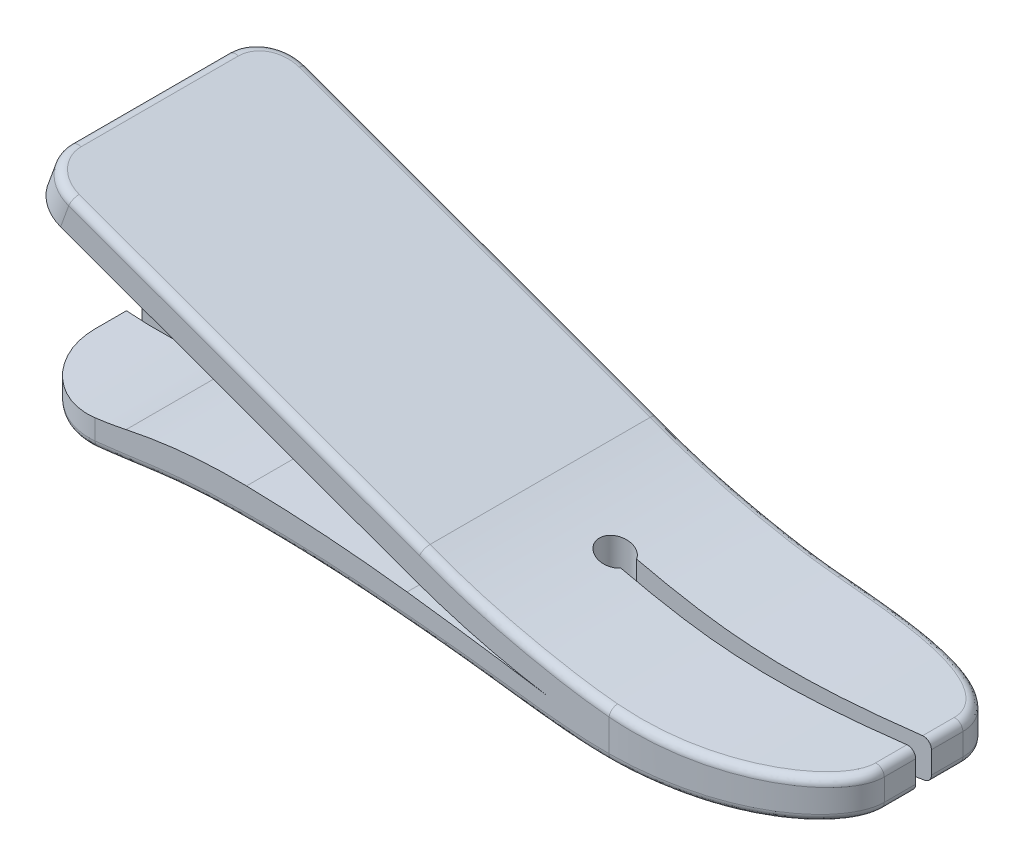
SolidWorks part; units mm, degrees
material "Thornel Mat VMA"
ref_plane "Front Plane" through (0, 0, 0) normal (0, 0, 1) x (1, 0, 0)
ref_plane "Top Plane" through (0, 0, 0) normal (0, 1, 0) x (1, 0, 0)
ref_plane "Right Plane" through (0, 0, 0) normal (1, 0, 0) x (0, 0, -1)
sketch "Sketch2" plane through (0, 0, 0) normal (0, 0, 1) x (1, 0, 0)
  line L0 (144.78, 174.4323) -> (144.78, 137.3355) construction
  line L1 (46.11, 139.37) -> (144.78, 103.46)
  line L2 (44.26, 97.84) -> (44.26, 91.84)
  line L3 (245.06, 96.26) -> (245.06, 92.26)
  line L4 (48.846, 146.8876) -> (147.516, 110.9776)
  line L5 (245.06, 101.76) -> (245.06, 96.26)
  line L6 (48.846, 146.8876) -> (46.11, 139.37)
  arc A0 (144.78, 103.46) -> (179.17, 94.55) centre (208.4691, 278.4588) ccw
  arc A3 (179.17, 94.55) -> (143.65, 99.57) centre (18.7037, -912.6868) ccw
  arc A4 (143.65, 99.57) -> (102.8, 102.5) centre (94.6418, -297.4717) ccw
  arc A5 (102.8, 102.5) -> (72.17, 99.6) centre (100.0611, -31.7796) ccw
  arc A6 (72.17, 99.6) -> (44.26, 97.84) centre (52.2393, 193.4826) cw
  spline S0 degree 3 poles (44.26, 91.84) (53.5686, 89.6988) (67.9986, 91.4707) (87.3947, 94.2323) (104.492, 94.6368) (123.2628, 94.2573) (142.8062, 92.7184) (161.4431, 90.8285) (176.9982, 88.6534) (190.5134, 87.509) (212.5929, 87.8654) (230.8283, 89.479) (245.06, 92.26) knots 0 0 0 0 0.139004 0.215092 0.291514 0.393025 0.494409 0.58308 0.671708 0.728105 0.784648 1 1 1 1
  spline S1 degree 3 poles (245.06, 101.76) (230.7908, 100.0488) (212.4954, 98.2461) (190.4741, 100.0364) (172.1057, 103.16) (157.7493, 106.9657) (147.516, 110.9776) knots 0 0 0 0 0.436365 0.551893 0.667816 1 1 1 1
  point P0 (44.26, 97.84)
  point P1 (72.17, 99.6)
  point P2 (102.8, 102.5)
  point P3 (143.65, 99.57)
  point P4 (179.17, 94.55)
  point P5 (201.9143, 92.75)
  point P6 (245.06, 96.26)
  point P7 (144.78, 103.46)
  point P10 (46.11, 139.37)
  point P27 (161.7621, 98.1831)
  point P28 (161.4321, 97.2162)
  point P29 (190.5094, 93.2003)
  point P30 (223.5612, 93.6297)
  point P31 (123.2625, 101.5581)
  point P32 (87.4017, 101.93)
  point P33 (58.2794, 97.698)
  point P34 (44.26, 91.84)
  point P35 (58.2794, 90.698)
  point P36 (72.17, 92.1)
  point P37 (87.4017, 93.93)
  point P38 (102.8, 94.5)
  point P39 (123.2625, 94.0581)
  point P40 (143.65, 92.57)
  point P41 (161.4321, 90.7162)
  point P42 (179.17, 88.55)
  point P43 (190.5094, 87.7003)
  point P44 (201.9098, 87.75)
  point P45 (223.5612, 89.1297)
  point P46 (245.06, 92.26)
  point P53 (161.7621, 106.1831)
  point P55 (179.17, 102.05)
  point P57 (245.06, 101.76)
  point P59 (223.5612, 99.6297)
  point P61 (201.92, 99.25)
  point P63 (190.5094, 100.2003)
  dimension "D1" = 70.002
  dimension "D2" = 105.0014
  dimension "D3" = 6
  dimension "D4" = 7
  dimension "D5" = 7.5
  dimension "D6" = 8
  dimension "D7" = 8
  dimension "D8" = 7.5
  dimension "D9" = 7
  dimension "D10" = 6.5
  dimension "D11" = 6
  dimension "D12" = 5.5
  dimension "D13" = 5
  dimension "D14" = 4.5
  dimension "D15" = 4
  dimension "D17" = 8
  dimension "D18" = 7.5
  dimension "D19" = 7
  dimension "D20" = 6.5
  dimension "D21" = 6
  dimension "D22" = 5.5
  dimension "D16" = 8
extrude "Boss-Extrude1" add sketch "Sketch2" along normal blind 60
fillet "Fillet1" radius 20 1 edges at (245.06, 97.01, 60) second distance 50 first distance on face at (245.06, 97.01, 30)
fillet "Fillet2" radius 50 1 edges at (245.06, 97.01, 0) second distance 20 first distance on face at (117.6568, 106.2926, 0)
fillet "Fillet3" radius 20 2 edges at (44.26, 94.84, 0) (44.26, 94.84, 60)
fillet "Fillet4" radius 10 2 edges at (47.478, 143.1288, 0) (47.478, 143.1288, 60)
sketch "Sketch3" plane through (0, 0, 0) normal (0, 1, 0) x (1, 0, 0)
  line L0 (245.06, -30) -> (99.6164, -30) construction
  line L1 (245.06, -40) -> (245.06, -20) construction
  line L2 (245.06, -28) -> (245.06, -32)
  line L3 (245.06, -28) -> (170.06, -28)
  line L4 (245.06, -32) -> (170.06, -32)
  line L6 (44.26, -30) -> (68.7821, -30) construction
  line L7 (44.26, -40) -> (44.26, -20) construction
  line L8 (44.26, -28) -> (44.26, -32)
  line L9 (44.26, -28) -> (119.26, -28)
  line L10 (44.26, -32) -> (119.26, -32)
  arc A0 (170.06, -28) -> (170.06, -32) centre (166.5959, -30) ccw
  arc A1 (119.26, -32) -> (119.26, -28) centre (122.7241, -30) ccw
  dimension "D1" = 75
  dimension "D2" = 4
  dimension "D3" = 2
  dimension "D4" = 4
  dimension "D5" = 75
  dimension "D6" = 2
extrude "Cut-Extrude1" cut sketch "Sketch3" along normal up to next
fillet "Fillet5" radius 2 11 edges at (102.8795, 127.2226, 0) (51.5983, 145.8859, 2.9289) (48.846, 146.8876, 30) (51.5983, 145.8859, 57.0711) (102.8795, 127.2226, 60)
fillet "Fillet6" radius 2 10 edges at (44.26, 91.84, 24) (48.5381, 91.076, 7.6378) (44.26, 91.84, 36) (52.009, 90.7489, 55.8087)
sketch "Sketch4" plane through (0, 0, 60) normal (0, 0, 1) x (1, 0, 0)
  line L0 (57.559, 141.5883) -> (57.559, 175.437)
